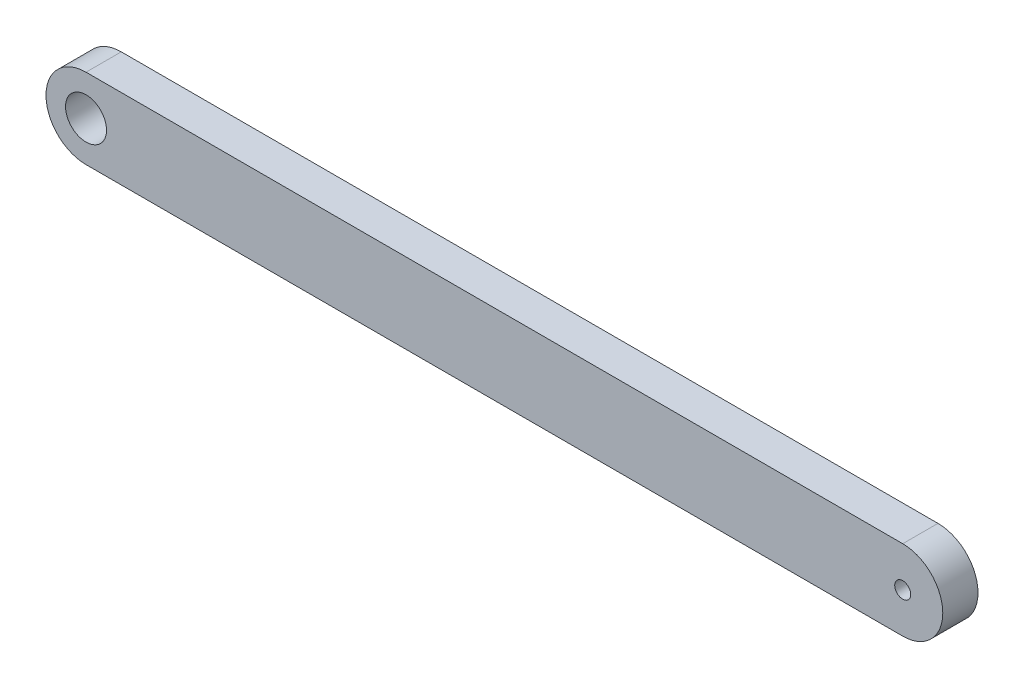
SolidWorks part; units mm, degrees
ref_plane "Front Plane" through (0, 0, 0) normal (0, 0, 1) x (1, 0, 0)
ref_plane "Top Plane" through (0, 0, 0) normal (0, 1, 0) x (1, 0, 0)
ref_plane "Right Plane" through (0, 0, 0) normal (1, 0, 0) x (0, 0, -1)
sketch "Sketch1" plane through (0, 0, 0) normal (0, 0, 1) x (1, 0, 0)
  line L0 (0, 0) -> (63.75, 0) construction
  line L1 (0, 3.125) -> (63.75, 3.125)
  line L2 (0, -3.125) -> (63.75, -3.125)
  arc A0 (0, 3.125) -> (0, -3.125) centre (0, 0) ccw
  arc A1 (63.75, -3.125) -> (63.75, 3.125) centre (63.75, 0) ccw
  circle A2 centre (0, 0) radius 1.6
  circle A3 centre (63.75, 0) radius 0.625
  point P3 (31.875, 0)
  dimension "D2" = 3.2
  dimension "D3" = 3.125
  dimension "D4" = 1.25
  dimension "D1" = 63.75
extrude "Boss-Extrude1" add sketch "Sketch1" along normal blind 2.75
